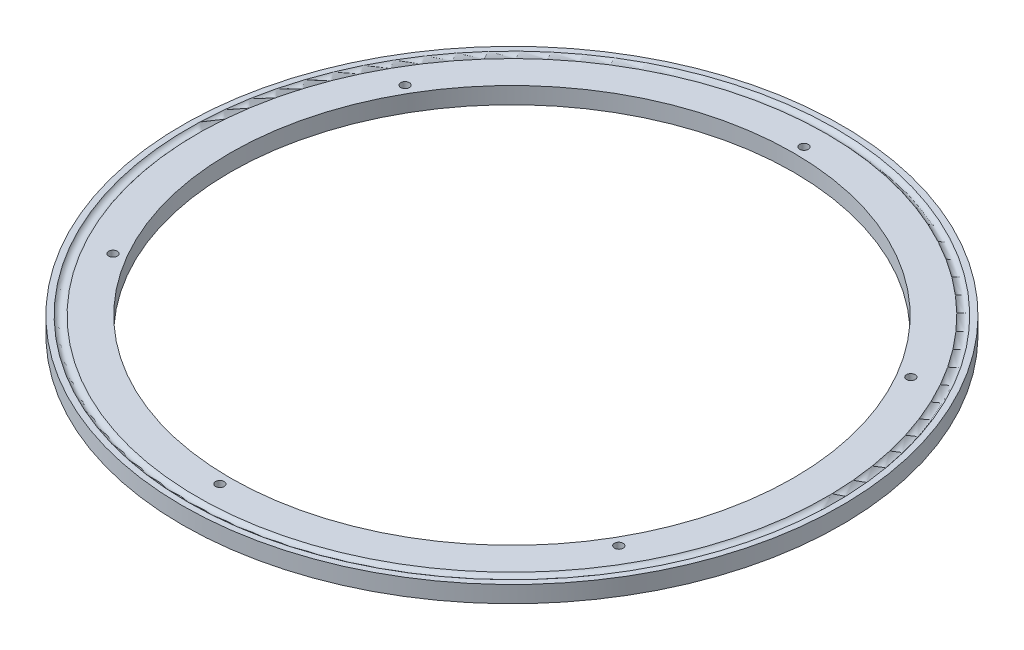
SolidWorks part; units mm, degrees
material "6061 Alloy"
ref_plane "Front Plane" through (0, 0, 0) normal (0, 0, 1) x (1, 0, 0)
ref_plane "Top Plane" through (0, 0, 0) normal (0, 1, 0) x (1, 0, 0)
ref_plane "Right Plane" through (0, 0, 0) normal (1, 0, 0) x (0, 0, -1)
sketch "Sketch1" plane through (0, 0, 0) normal (0, 1, 0) x (1, 0, 0)
  circle A0 centre (0, 0) radius 85.725
  circle A1 centre (0, 0) radius 100.33
  circle A2 centre (0, 0) radius 97.155
  circle A3 centre (0, -88.9) radius 1.3208
  circle A4 centre (-76.9897, -44.45) radius 1.3208
  circle A5 centre (-76.9897, 44.45) radius 1.3208
  circle A6 centre (0, 88.9) radius 1.3208
  circle A7 centre (76.9897, 44.45) radius 1.3208
  circle A8 centre (76.9897, -44.45) radius 1.3208
  point P21 (0, 0)
  dimension "D1" = 171.45
  dimension "D4" = 2.6416
  dimension "D5" = 88.9
  dimension "D2" = 14.605
  dimension "D3" = 11.43
  dimension "D6" = 6
extrude "Boss-Extrude1" add sketch "Sketch1" along normal blind 5.08 contours A2 A0 | A1 A2 region at (-97.4922, 0, 0) region at (-94.407, 0, 0)
sketch "Sketch2" plane through (0, 0, 0) normal (1, 0, 0) x (0, 0, -1)
  line L0 (-100.33, 0) -> (100.33, 0) construction
  line L1 (100.33, 5.08) -> (-100.33, 5.08) construction
  line L2 (-100.33, 0) -> (100.33, 0)
  line L3 (100.33, 5.08) -> (-100.33, 5.08)
  line L4 (89.5975, 4.318) -> (99.9841, 4.318) construction
  line L5 (95.9885, 2.54) -> (99.6739, 2.54) construction
  line L6 (0, 0) -> (0, 18.217) construction
  circle A0 centre (97.155, 5.9055) radius 1.5875 construction
  circle A1 centre (97.155, 5.969) radius 1.651
  circle A2 centre (97.155, -0.889) radius 1.651
  dimension "D3" = 3.175
  dimension "D4" = 3.302
  dimension "D1" = 97.155
  dimension "D2" = 0.762
  dimension "D5" = 2.54
revolve "Cut-Revolve1" cut sketch "Sketch2" angle 360 about L6 region at (0, 0.3118, -97.155) region at (0, 4.7682, -97.155)
equation "\"Middle Coupler Inner Daimeter\"= 6.75in"
equation "\"Middle Coupler  Wall Thickness\" = 0.25in"
equation "\"Middle Coupler Bottom Thickness\"= 0.2in"
equation "\"Bearing Rail Offset\"= 0.45in"
equation "\"3-56 UNF Tap\"= 0.089in"
equation "\"3-56 UNF Clearance\"= 0.104in"
equation "\"D5@Sketch1\"=(\"Middle Coupler Inner Daimeter\"*2+0.5)/4in"
equation "\"Ball Bearing Distance\"= 0.03in"
equation "\"D1@Sketch2\"=\"Middle Coupler Inner Daimeter\"/2+\"Bearing Rail Offset\""
equation "\"D3@Sketch1\"=\"Bearing Rail Offset\""
equation "\"D4@Sketch1\"=\"3-56 UNF Clearance\""
equation "\"D1@Sketch1\"=\"Middle Coupler Inner Daimeter\""
equation "\"D2@Sketch2\"=\"Ball Bearing Distance\""
equation "\"D4@Sketch2\"=\"D3@Sketch2\"+0.005"
equation "\"D5@Sketch2\"=\"Middle Coupler Bottom Thickness\"/2"
